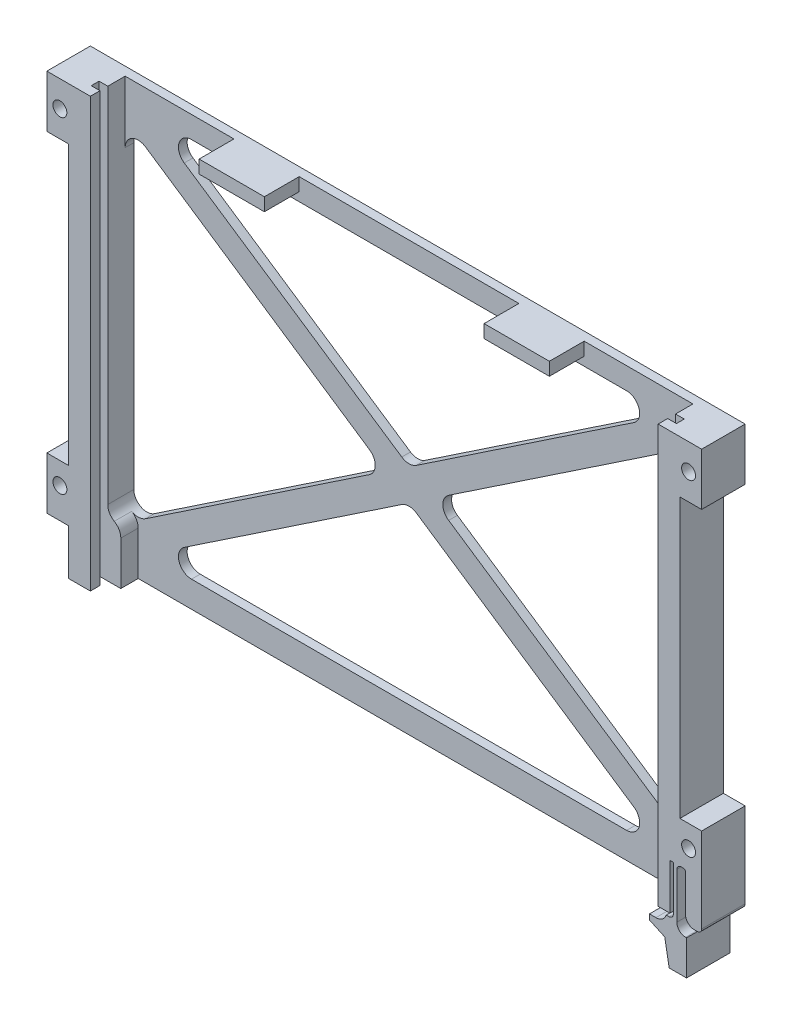
SolidWorks part; units mm, degrees
ref_plane "Front Plane" through (0, 0, 0) normal (0, 0, 1) x (1, 0, 0)
ref_plane "Top Plane" through (0, 0, 0) normal (0, 1, 0) x (1, 0, 0)
ref_plane "Right Plane" through (0, 0, 0) normal (1, 0, 0) x (0, 0, -1)
sketch "Sketch1" plane through (0, 0, 0) normal (0, 0, 1) x (1, 0, 0)
  line L1 (2.5, 0) -> (132, 0)
  line L2 (0, 2.5) -> (0, 93)
  line L3 (2.5, 95.5) -> (132, 95.5)
  line L4 (134.5, 2.5) -> (134.5, 93)
  arc A0 (2.5, 0) -> (0, 2.5) centre (2.5, 2.5) cw
  arc A1 (0, 93) -> (2.5, 95.5) centre (2.5, 93) cw
  arc A2 (132, 95.5) -> (134.5, 93) centre (132, 93) cw
  arc A3 (132, 0) -> (134.5, 2.5) centre (132, 2.5) ccw
  point P7 (0, 0)
  point P13 (134.5, 95.5)
  point P16 (134.5, 0)
  dimension "D3" = 2.5
  dimension "D1" = 134.5
  dimension "D2" = 95.5
sketch "Sketch2" plane through (0, 0, 0) normal (0, 0, 1) x (1, 0, 0)
  line L4 (2, 0) -> (-3, 0)
  line L6 (-3, 0) -> (-3, 98.5)
  line L7 (-3, 98.5) -> (137.5, 98.5)
  line L8 (137.5, 98.5) -> (137.5, 0)
  line L9 (137.5, 0) -> (132.5, 0)
  line L10 (2.5, 0) -> (132, 0) construction
  line L11 (134.5, 2.5) -> (134.5, 93) construction
  line L16 (2.5, 95.5) -> (132, 95.5) construction
  line L18 (0, 2.5) -> (0, 93) construction
  line L20 (2, 93.5) -> (132.5, 93.5)
  line L21 (2, 93.5) -> (2, 0)
  line L23 (132.5, 93.5) -> (132.5, 0)
  point P16 (0, 0)
  point P17 (7.4742, 87.3384)
  dimension "D1" = 3
  dimension "D2" = 3
  dimension "D3" = 3
  dimension "D4" = 2
  dimension "D5" = 2
  dimension "D6" = 2
extrude "Boss-Extrude1" add sketch "Sketch2" along normal blind 10
sketch "Sketch3" plane through (0, 0, 0) normal (0, -1, 0) x (1, 0, 0)
  line L0 (67.25, 6) -> (67.25, 10)
  line L10 (0, 7.8) -> (134.5, 7.8)
  line L11 (0, 7.8) -> (0, 6)
  line L12 (0, 6) -> (134.5, 6)
  line L13 (134.5, 7.8) -> (134.5, 6)
  line L16 (132.5, 0) -> (137.5, 0) construction
  line L17 (2, 10) -> (132.5, 10) construction
  point P7 (0, 0)
  point P12 (0, 0)
  point P14 (67.25, 10)
  dimension "D1" = 1.8
  dimension "D2" = 6
extrude "Cut-Extrude1" cut sketch "Sketch3" against normal through all contours L10 L13 L12 L11
sketch "Sketch6" plane through (0, 0, 0) normal (0, 0, 1) x (1, 0, 0)
  line L0 (67.25, 98.5) -> (67.25, 12.3809) construction
  line L1 (-5, 92.5) -> (139.5, 92.5) construction
  line L2 (-5, 92.5) -> (-5, 17.5) construction
  line L3 (-5, 17.5) -> (139.5, 17.5) construction
  line L4 (139.5, 92.5) -> (139.5, 17.5) construction
  line L5 (137.5, 98.5) -> (-3, 98.5) construction
  line L6 (137.5, 0) -> (137.5, 98.5) construction
  circle A0 centre (-5, 92.5) radius 1.6
  circle A1 centre (139.5, 92.5) radius 1.6
  circle A2 centre (-5, 17.5) radius 1.6
  circle A3 centre (139.5, 17.5) radius 1.6
  dimension "D1" = 6
  dimension "D4" = 3.2
  dimension "D2" = 2
  dimension "D3" = 75
sketch "Sketch5" plane through (0, 0, 0) normal (0, 0, -1) x (-1, 0, 0)
  line L0 (-137.5, 0) -> (-137.5, 98.5) construction
  line L1 (3, 0) -> (-137.5, 0)
  line L2 (3, 0) -> (3, 6)
  line L3 (3, 6) -> (-137.5, 6)
  line L4 (-137.5, 0) -> (-137.5, 6)
  line L6 (-2, 6) -> (-132.5, 93.5) construction
  line L7 (-2, 0) -> (-2, 93.5) construction
  line L8 (-2, 93.5) -> (-132.5, 6) construction
  line L9 (-132.5, 93.5) -> (-132.5, 0) construction
  line L10 (-0.3293, 8.4917) -> (-130.8293, 95.9917)
  line L11 (-3.6707, 95.9917) -> (-134.1707, 8.4917)
  line L12 (-3.6707, 3.5083) -> (-134.1707, 91.0083)
  line L13 (-0.3293, 91.0083) -> (-130.8293, 3.5083)
  line L14 (-0.3293, 8.4917) -> (-3.6707, 3.5083)
  line L15 (-130.8293, 95.9917) -> (-134.1707, 91.0083)
  line L16 (-3.6707, 95.9917) -> (-0.3293, 91.0083)
  line L17 (-134.1707, 8.4917) -> (-130.8293, 3.5083)
  point P15 (-132.5, 6)
  dimension "D1" = 6
  dimension "D2" = 3
  dimension "D3" = 3
extrude "Boss-Extrude3" add sketch "Sketch5" against normal blind 2 contours L10 L15 L12 L14 | L11 L17 L13 L16 | L3 L4 L1 L2
sketch "Sketch4" plane through (0, 0, 0) normal (0, 0, 1) x (1, 0, 0)
  line L0 (134.3685, 1.7) -> (135, 1.7)
  line L1 (138.8, -0.5) -> (139.0272, -0.5)
  line L2 (136, 2.7) -> (136, 13)
  line L3 (135.2, 13) -> (136, 13)
  line L4 (136.8, 12) -> (136.8, 1.5)
  line L6 (135.0272, -8.5) -> (134.0272, -2.837)
  line L7 (134.0272, -2.837) -> (130.5, -1.2)
  line L8 (130.5, -1.2) -> (130.5, 0)
  line L9 (134.5, 2.5) -> (134.5, 93) construction
  line L10 (139.0272, -0.5) -> (139.0272, -8.5)
  line L11 (139.0272, -8.5) -> (135.0272, -8.5)
  line L12 (132.5, 0) -> (137.5, 0) construction
  line L13 (137.8, 13) -> (138.3, 13)
  line L14 (138.8, 12.5) -> (138.8, 4)
  line L15 (140.8, 2) -> (141.5, 2)
  line L16 (142.5, 3) -> (142.5, 22.5)
  line L17 (142.5, 22.5) -> (137.5, 22.5)
  line L18 (137.5, 0) -> (137.5, 98.5) construction
  line L19 (129.5, 2.5) -> (135.2, 2.5)
  line L20 (135.2, 2.5) -> (135.2, 13)
  line L21 (135.2, 2.7) -> (135.2, 13) construction
  line L22 (134.3685, 2.5) -> (135, 2.5) construction
  line L23 (129.5, 2.5) -> (129.5, 0)
  line L24 (139.0272, -0.5) -> (142.5, -0.5)
  line L25 (132.5, 93.5) -> (132.5, 0) construction
  line L26 (137.5, 22.5) -> (136, 22.5)
  line L27 (136, 22.5) -> (136, 13)
  line L28 (142.5, -0.5) -> (142.5, 3)
  line L29 (2.5, 0) -> (132, 0) construction
  line L30 (130.5, 0) -> (132, 0)
  line L31 (129.5, 0) -> (130.5, 0)
  line L33 (67.25, 98.5) -> (67.25, 12.3809) construction
  line L34 (137.5, 98.5) -> (142.5, 98.5)
  line L35 (137.5, 98.5) -> (137.5, 86.5)
  line L36 (137.5, 86.5) -> (142.5, 86.5)
  line L37 (142.5, 98.5) -> (142.5, 86.5)
  line L38 (67.25, 98.5) -> (67.25, 12.3809) construction
  line L39 (-8, 98.5) -> (-8, 86.5)
  line L40 (-3, 86.5) -> (-8, 86.5)
  line L41 (-3, 98.5) -> (-3, 86.5)
  line L42 (-3, 98.5) -> (-8, 98.5)
  line L43 (-3, 98.5) -> (-3, 0) construction
  line L44 (-8, 22.5) -> (-3, 22.5)
  line L45 (-8, 22.5) -> (-8, 10.5)
  line L46 (-8, 10.5) -> (-3, 10.5)
  line L47 (-3, 22.5) -> (-3, 10.5)
  arc A0 (132, 0) -> (134.5, 2.5) centre (132, 2.5) ccw construction
  arc A1 (132, 0) -> (134.3685, 1.7) centre (132, 2.5) ccw
  arc A2 (138.8, -0.5) -> (136.8, 1.5) centre (138.8, 1.5) cw
  arc A3 (135, 1.7) -> (136, 2.7) centre (135, 2.7) ccw
  arc A4 (138.8, 4) -> (140.8, 2) centre (140.8, 4) ccw
  arc A5 (136.8, 12) -> (137.8, 13) centre (137.8, 12) cw
  arc A6 (138.8, 12.5) -> (138.3, 13) centre (138.3, 12.5) ccw
  arc A7 (141.5, 2) -> (142.5, 3) centre (141.5, 3) ccw
  circle A9 centre (139.5, 17.5) radius 2.75 construction
  circle A10 centre (139.5, 92.5) radius 1.6 construction
  circle A11 centre (-5, 17.5) radius 1.6 construction
  circle A12 centre (-5, 92.5) radius 1.6 construction
  circle A13 centre (139.5, 92.5) radius 1.6
  circle A14 centre (-5, 17.5) radius 1.6
  circle A15 centre (-5, 92.5) radius 1.6
  circle A16 centre (139.5, 17.5) radius 1.6 construction
  circle A17 centre (139.5, 17.5) radius 1.6
  point P44 (131.5, -0.0607)
  point P45 (133.8537, -2.5966)
  point P56 (131.3831, -0.0536)
  point P63 (0, 0)
  point P72 (133.9159, -4.173)
  point P88 (133.8788, -3.3936)
  point P90 (134.0272, -2.837)
  dimension "D7" = 2
  dimension "D8" = 1
  dimension "D13" = 2
  dimension "D14" = 1
  dimension "D15" = 0.5
  dimension "D20" = 1
  dimension "D25" = 5.5
  dimension "D3" = 1.5
  dimension "D4" = 4
  dimension "D5" = 13
  dimension "D6" = 8
  dimension "D9" = 1.2
  dimension "D10" = 8.5
  dimension "D11" = 5
  dimension "D12" = 2
  dimension "D17" = 0.8
  dimension "D19" = 11
  dimension "D21" = 10
  dimension "D18" = 2.5
  dimension "D26" = 1
  dimension "D23" = 12
  dimension "D24" = 5
  dimension "D22" = 4
  dimension "D16" = 0.8
extrude "Cut-Extrude2" cut sketch "Sketch4" along normal through all
fillet "Fillet1" radius 3 12 edges at (7.387, 6, 1) (67.25, 46.1381, 1) (127.113, 6, 1) (132.5, 9.6119, 1) (72.637, 49.75, 1) (132.5, 89.8881, 1) (67.25, 53.3619, 1) (7.387, 93.5, 1) (2, 89.8881, 1) (61.863, 49.75, 1) (2, 9.6119, 1) (127.113, 93.5, 1)
extrude "Boss-Extrude2" add sketch "Sketch4<3>" along normal through all contours L15 A7 L16 L17 L26 L27 L2 A3 L0 A1 L8 L7 L6 L11 L10 L1 A2 L4 A5 L13 A6 L14 A4 | L37 L34 L35 L36 A13 | L41 L42 L39 L40 A15 | L47 L44 L45 L46 A14 region at (134.6843, 1.3676, 0) region at (140, 98.37, 0) region at (-5.5, 98.37, 0) region at (-5.5, 22.37, 0)
sketch "Sketch4<3>" plane through (0, 0, 0) normal (0, 0, 1) x (1, 0, 0) same geometry as "Sketch4"
sketch "Sketch7" plane through (0, 0, 10) normal (0, 0, 1) x (1, 0, 0)
  line L0 (142.5, 98.5) -> (-8, 98.5) construction
  line L1 (2, 93.5) -> (132.5, 93.5)
  line L2 (2, 93.5) -> (2, 98.5)
  line L3 (2, 98.5) -> (132.5, 98.5)
  line L4 (132.5, 93.5) -> (132.5, 98.5)
  point P7 (132.5, 93.5)
extrude "Cut-Extrude3" cut sketch "Sketch7" against normal up to surface (8 mm away) up to face at (67.25, 20.7149, 2)
sketch "Sketch8" plane through (0, 0, 2) normal (0, 0, 1) x (1, 0, 0)
  line L7 (2, 98.5) -> (132.5, 98.5) construction
  line L8 (27, 98.5) -> (42, 98.5)
  line L9 (27, 98.5) -> (27, 95.5)
  line L10 (27, 95.5) -> (42, 95.5)
  line L11 (42, 98.5) -> (42, 95.5)
  line L12 (2.5, 95.5) -> (132, 95.5) construction
  line L13 (67.25, 98.5) -> (67.25, 12.3809) construction
  line L14 (67.25, 98.5) -> (67.25, 12.3809) construction
  line L15 (92.5, 98.5) -> (92.5, 95.5)
  line L16 (107.5, 95.5) -> (92.5, 95.5)
  line L17 (107.5, 98.5) -> (107.5, 95.5)
  line L18 (107.5, 98.5) -> (92.5, 98.5)
  line L19 (2, 0) -> (2, 98.5) construction
  dimension "D1" = 15
  dimension "D2" = 25
extrude "Boss-Extrude4" add sketch "Sketch8" along normal up to surface (8 mm away) up to face at (-3.4, 17.5, 10)
sketch "Sketch9" plane through (0, 0, 2) normal (0, 0, 1) x (1, 0, 0)
  line L0 (129.5, 12.2354) -> (129.5, 2.5)
  line L1 (129.5, 2.5) -> (132.5, 2.5)
  line L4 (2, 0) -> (5, 0)
  line L5 (2, 0) -> (129.5, 0) construction
  line L6 (5, 0) -> (5, 12.2354)
  line L9 (2, 15.2354) -> (2, 0)
  arc A0 (127.8293, 12.7436) -> (132.5, 15.2354) centre (129.5, 15.2354) ccw construction
  arc A1 (129.5, 12.2354) -> (132.5, 15.2354) centre (129.5, 15.2354) ccw
  arc A2 (2, 15.2354) -> (6.6707, 12.7436) centre (5, 15.2354) ccw construction
  arc A3 (2, 15.2354) -> (5, 12.2354) centre (5, 15.2354) ccw
  line M29 (58.1468, 47.2583) -> (6.6707, 12.7436)
  arc M30 (6.6707, 12.7436) -> (2, 15.2354) centre (5, 15.2354) cw
  line M31 (2, 15.2354) -> (2, 0)
  line M32 (2, 0) -> (129.5, 0)
  line M34 (129.5, 2.5) -> (132.5, 2.5)
  line M35 (132.5, 2.5) -> (132.5, 15.2354)
  arc M36 (132.5, 15.2354) -> (127.8293, 12.7436) centre (129.5, 15.2354) cw
  line M37 (127.8293, 12.7436) -> (76.3532, 47.2583)
  dimension "D1" = 3
  dimension "D2" = 3
extrude "Boss-Extrude5" add sketch "Sketch9" along normal up to surface (4 mm away) contours L6 M32 M29 M30 M31 | L0 L1 M34 M35 M36 M37 region at (131.0515, 7.7112, 2) region at (3.4585, 6.457, 2) up to face at (1, 49.25, 6)
fillet "Fillet2" radius 3 2 edges at (129.5, 12.2354, 4) (5, 12.2354, 4)
equation "\"D2@Sketch2\"=\"D1@Sketch2\""
equation "\"D3@Sketch2\"=\"D1@Sketch2\""
equation "\"D5@Sketch2\"=\"D4@Sketch2\""
equation "\"D6@Sketch2\"=\"D4@Sketch2\""
equation "\"D16@Sketch4\"=\"D17@Sketch4\""
equation "\"D2@Sketch9\"=\"D1@Sketch9\""
